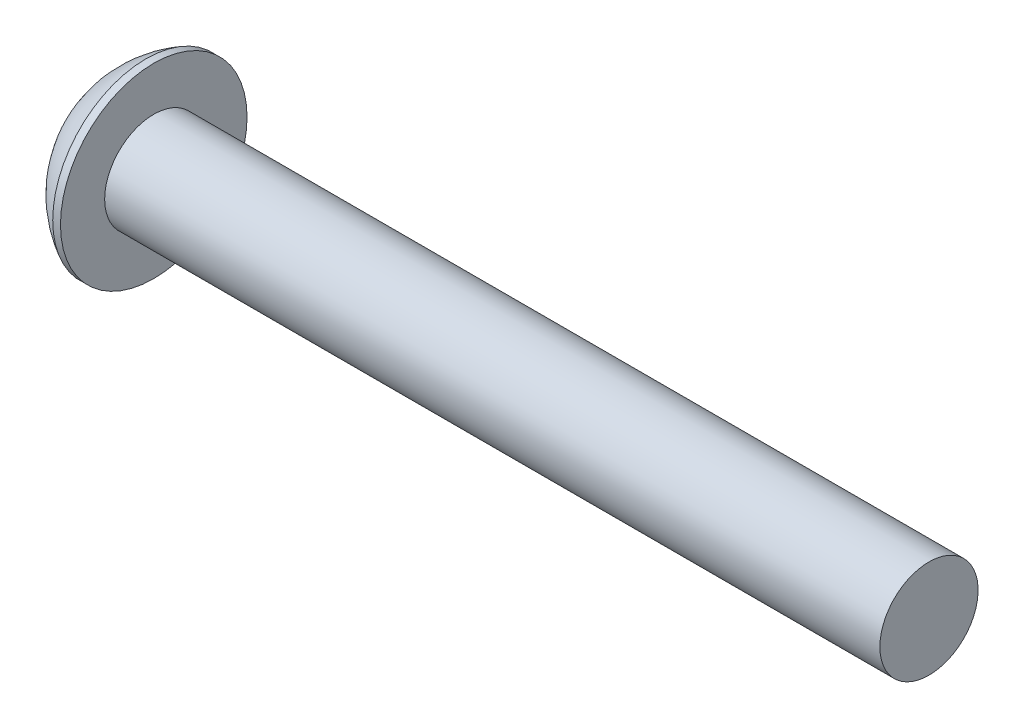
SolidWorks part; units mm, degrees
material "Alloy Steel"
ref_plane "Front" through (0, 0, 0) normal (0, 0, 1) x (1, 0, 0)
ref_plane "Top" through (0, 0, 0) normal (0, 1, 0) x (1, 0, 0)
ref_plane "Right" through (0, 0, 0) normal (1, 0, 0) x (0, 0, -1)
sketch "Sketch1" plane through (0, 0, 0) normal (0, 0, 1) x (1, 0, 0)
  line L0 (0, 0) -> (38.8366, 0)
  line L1 (38.8366, 0) -> (38.8366, 2.413)
  line L2 (38.8366, 2.413) -> (0.7366, 2.413)
  line L3 (0.7366, 2.413) -> (0.7366, 4.5847)
  line L4 (0.7366, 4.5847) -> (0.3556, 4.5847)
  line L5 (-1.8288, 2.413) -> (-1.8288, 1.8288)
  line L6 (0, 0) -> (4.2959, 0) construction
  line L7 (-1.8288, 1.8288) -> (0, 0)
  arc A0 (-1.8288, 2.413) -> (0.3556, 4.5847) centre (2.7515, -0.0097) cw
  dimension "Head Radius" = 5.1816
  dimension "Edge Flat" = 0.381
  dimension "Thread Length" = 38.1
  dimension "Head Diameter" = 9.1694
  dimension "Thread Diameter" = 4.826
  dimension "D6" = 45
  dimension "Head Height" = 2.5654
  dimension "Hex Chamfer Radius" = 1.8288
revolve "Revolve1" add sketch "Sketch1" angle 360 about L6
sketch "Sketch2" plane through (-1.8288, 0, 0) normal (-1, 0, 0) x (0, 0, 1)
  line L1 (1.8331, 0) -> (0.9165, 1.5875)
  line L2 (0.9165, 1.5875) -> (-0.9165, 1.5875)
  line L3 (-0.9165, 1.5875) -> (-1.8331, 0)
  line L4 (-1.8331, 0) -> (-0.9165, -1.5875)
  line L5 (-0.9165, -1.5875) -> (0.9165, -1.5875)
  line L6 (0.9165, -1.5875) -> (1.8331, 0)
  circle A0 centre (0, 0) radius 1.5875 construction
  dimension "Hex Width" = 3.175
extrude "Cut-Extrude1" cut sketch "Sketch2" against normal up to vertex (1.8288 mm away) up to point (0, 0, 0)
